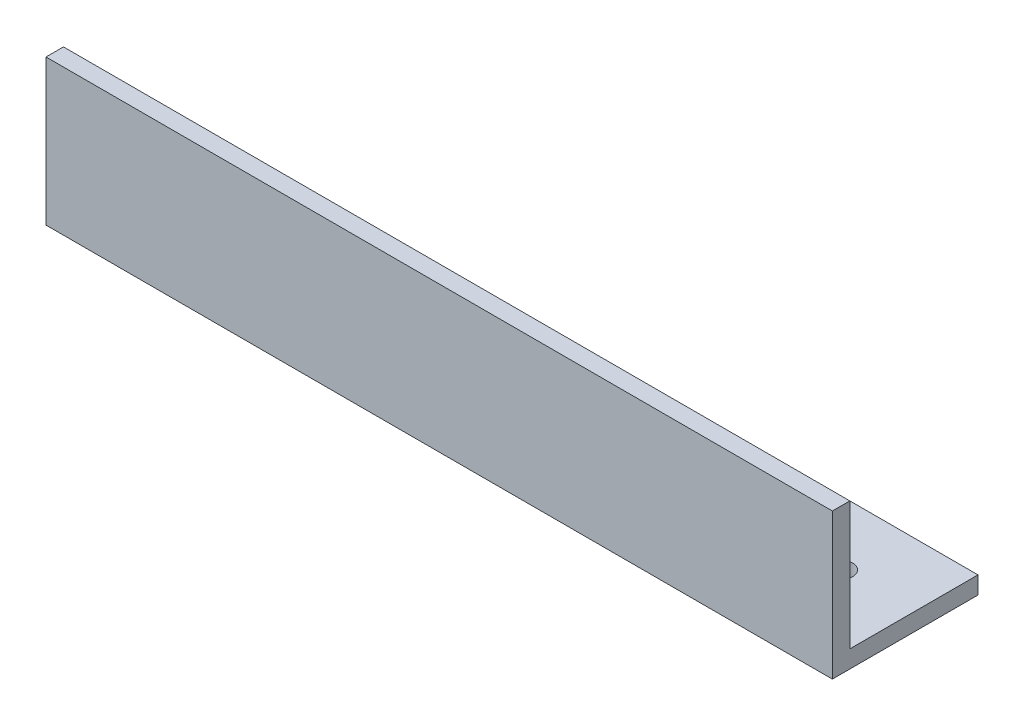
SolidWorks part; units mm, degrees
ref_plane "Спереди" through (0, 0, 0) normal (0, 0, 1) x (1, 0, 0)
ref_plane "Сверху" through (0, 0, 0) normal (0, 1, 0) x (1, 0, 0)
ref_plane "Справа" through (0, 0, 0) normal (1, 0, 0) x (0, 0, -1)
sketch "Эскиз1" plane through (0, 0, 0) normal (1, 0, 0) x (0, 0, -1)
  line L0 (0, 0) -> (50, 0)
  line L5 (0, 50) -> (0, 0)
extrude "Вытянуть-Тонкостенный2" add sketch "Эскиз1" along normal blind 270 thin thin type one direction reverse wall 6
sketch "Эскиз2" plane through (0, 0, 0) normal (0, -1, 0) x (1, 0, 0)
  line L0 (135, 0) -> (135, -56.3824) construction
  line L1 (270, 0) -> (0, 0) construction
  circle A0 centre (25, -28) radius 4
  circle A1 centre (245, -28) radius 4
extrude "Вырез-Вытянуть1" cut sketch "Эскиз2" against normal through all
